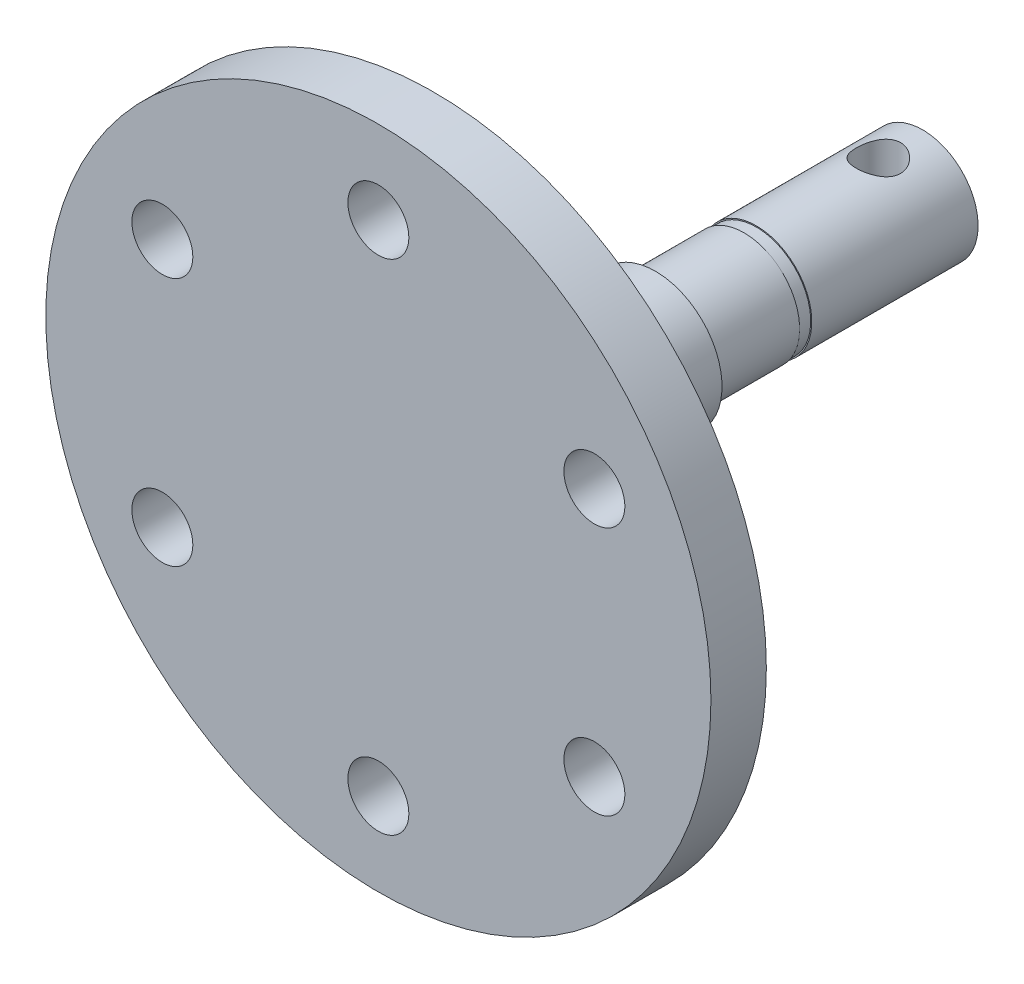
SolidWorks part; units mm, degrees
ref_plane "前视基准面" through (0, 0, 0) normal (0, 0, 1) x (1, 0, 0)
ref_plane "上视基准面" through (0, 0, 0) normal (0, 1, 0) x (1, 0, 0)
ref_plane "右视基准面" through (0, 0, 0) normal (1, 0, 0) x (0, 0, -1)
sketch "草图1" plane through (0, 0, 0) normal (0, 0, 1) x (1, 0, 0)
  line L0 (0, 22.5) -> (0, -22.5) construction
  line L1 (-19.4856, -11.25) -> (19.4856, 11.25) construction
  line L2 (-19.4856, 11.25) -> (19.4856, -11.25) construction
  circle A0 centre (0, 0) radius 30
  circle A1 centre (0, 0) radius 22.5 construction
  circle A2 centre (0, 22.5) radius 2.75
  circle A3 centre (19.4856, 11.25) radius 2.75
  circle A4 centre (19.4856, -11.25) radius 2.75
  circle A5 centre (0, -22.5) radius 2.75
  circle A6 centre (-19.4856, -11.25) radius 2.75
  circle A7 centre (-19.4856, 11.25) radius 2.75
  dimension "D1" = 60
  dimension "D2" = 45
  dimension "D5" = 5.5
  dimension "D6" = 5.5
  dimension "D7" = 5.5
  dimension "D8" = 5.5
  dimension "D9" = 5.5
  dimension "D10" = 5.5
  dimension "D3" = 60
  dimension "D4" = 60
extrude "凸台-拉伸1" add sketch "草图1" along normal blind 5
sketch "草图2" plane through (0, 0, 0) normal (0, 0, -1) x (-1, 0, 0)
  circle A0 centre (0, 0) radius 12
  dimension "D1" = 24
extrude "凸台-拉伸2" add sketch "草图2" along normal blind 10
sketch "草图3" plane through (0, 0, -10) normal (0, 0, -1) x (-1, 0, 0)
  circle A0 centre (0, 0) radius 6
  dimension "D1" = 12
extrude "凸台-拉伸3" add sketch "草图3" along normal blind 10
sketch "草图4" plane through (0, 0, -20) normal (0, 0, -1) x (-1, 0, 0)
  circle A0 centre (0, 0) radius 5
  dimension "D1" = 10
extrude "凸台-拉伸4" add sketch "草图4" along normal blind 8
sketch "草图5" plane through (0, 0, -28) normal (0, 0, -1) x (-1, 0, 0)
  circle A0 centre (0, 0) radius 4.9
  dimension "D1" = 9.8
extrude "凸台-拉伸5" add sketch "草图5" along normal blind 1.1
sketch "草图6" plane through (0, 0, -29.1) normal (0, 0, -1) x (-1, 0, 0)
  circle A0 centre (0, 0) radius 5
  dimension "D1" = 10
extrude "凸台-拉伸6" add sketch "草图6" along normal blind 15
sketch "草图7" plane through (0, 0, 0) normal (0, 1, 0) x (1, 0, 0)
  line L0 (5, 44.1) -> (-5, 44.1) construction
  circle A0 centre (0, 40.1) radius 2
  dimension "D2" = 4
  dimension "D1" = 4
extrude "切除-拉伸1" cut sketch "草图7" against normal blind 15 and the other way blind 15
